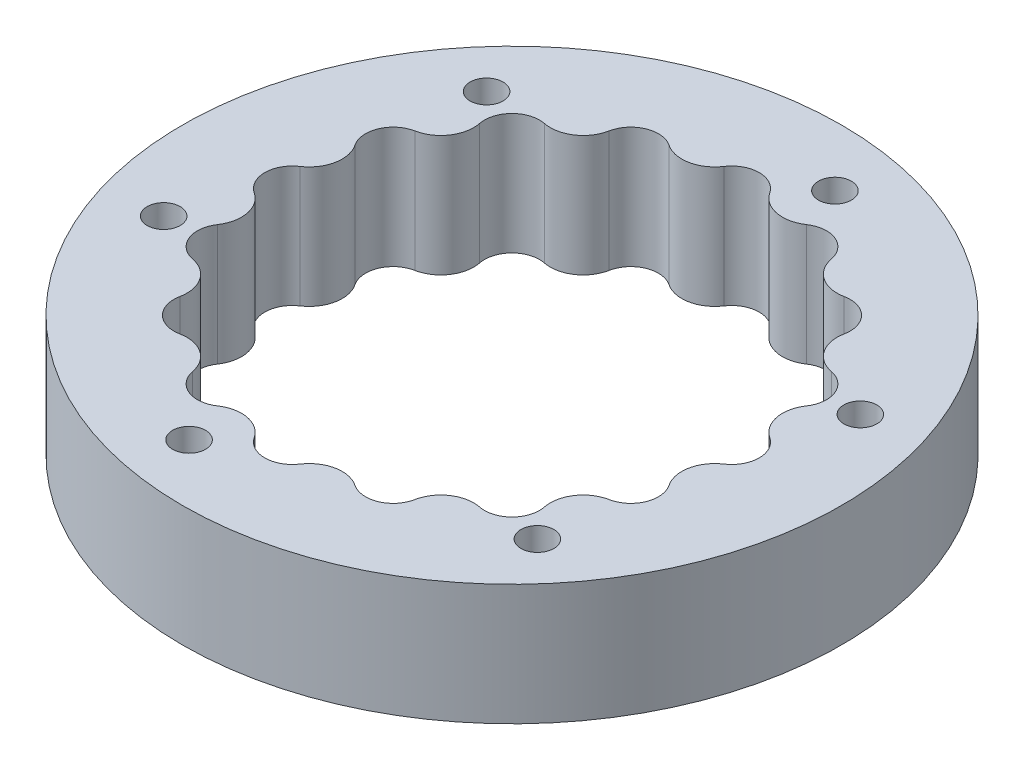
SolidWorks part; units mm, degrees
ref_plane "Front Plane" through (0, 0, 0) normal (0, 0, 1) x (1, 0, 0)
ref_plane "Top Plane" through (0, 0, 0) normal (0, 1, 0) x (1, 0, 0)
ref_plane "Right Plane" through (0, 0, 0) normal (1, 0, 0) x (0, 0, -1)
sketch "Sketch1" plane through (0, 0, 0) normal (0, 1, 0) x (1, 0, 0)
  arc A0 (-31.5919, 24.5347) -> (-34.7568, 19.7981) centre (0, 0) ccw
  arc A1 (4.9902, 39.6875) -> (-4.9902, 39.6875) centre (0, 40) ccw
  arc A2 (19.7981, 34.7568) -> (10.5774, 38.5761) centre (15.3073, 36.9552) ccw
  arc A3 (-31.5919, 24.5347) -> (-34.7568, 19.7981) centre (0, 0) ccw construction
  arc A4 (31.5919, 24.5347) -> (24.5347, 31.5919) centre (28.2843, 28.2843) ccw
  arc A5 (-31.5919, 24.5347) -> (-34.7568, 19.7981) centre (0, 0) ccw construction
  arc A6 (38.5761, 10.5774) -> (34.7568, 19.7981) centre (36.9552, 15.3073) ccw
  arc A7 (-31.5919, 24.5347) -> (-34.7568, 19.7981) centre (0, 0) ccw construction
  arc A8 (39.6875, -4.9902) -> (39.6875, 4.9902) centre (40, 0) ccw
  arc A9 (-31.5919, 24.5347) -> (-34.7568, 19.7981) centre (0, 0) ccw construction
  arc A10 (34.7568, -19.7981) -> (38.5761, -10.5774) centre (36.9552, -15.3073) ccw
  arc A11 (-31.5919, 24.5347) -> (-34.7568, 19.7981) centre (0, 0) ccw construction
  arc A12 (24.5347, -31.5919) -> (31.5919, -24.5347) centre (28.2843, -28.2843) ccw
  arc A13 (-31.5919, 24.5347) -> (-34.7568, 19.7981) centre (0, 0) ccw construction
  arc A14 (10.5774, -38.5761) -> (19.7981, -34.7568) centre (15.3073, -36.9552) ccw
  arc A15 (-31.5919, 24.5347) -> (-34.7568, 19.7981) centre (0, 0) ccw construction
  arc A16 (-4.9902, -39.6875) -> (4.9902, -39.6875) centre (0, -40) ccw
  arc A17 (-31.5919, 24.5347) -> (-34.7568, 19.7981) centre (0, 0) ccw construction
  arc A18 (-19.7981, -34.7568) -> (-10.5774, -38.5761) centre (-15.3073, -36.9552) ccw
  arc A19 (-31.5919, 24.5347) -> (-34.7568, 19.7981) centre (0, 0) ccw construction
  arc A20 (-31.5919, -24.5347) -> (-24.5347, -31.5919) centre (-28.2843, -28.2843) ccw
  arc A21 (-31.5919, 24.5347) -> (-34.7568, 19.7981) centre (0, 0) ccw construction
  arc A22 (-38.5761, -10.5774) -> (-34.7568, -19.7981) centre (-36.9552, -15.3073) ccw
  arc A23 (-31.5919, 24.5347) -> (-34.7568, 19.7981) centre (0, 0) ccw construction
  arc A24 (-39.6875, 4.9902) -> (-39.6875, -4.9902) centre (-40, 0) ccw
  arc A25 (-31.5919, 24.5347) -> (-34.7568, 19.7981) centre (0, 0) ccw construction
  arc A26 (-34.7568, 19.7981) -> (-38.5761, 10.5774) centre (-36.9552, 15.3073) ccw
  arc A27 (-31.5919, 24.5347) -> (-34.7568, 19.7981) centre (0, 0) ccw construction
  arc A28 (-24.5347, 31.5919) -> (-31.5919, 24.5347) centre (-28.2843, 28.2843) ccw
  arc A29 (-31.5919, 24.5347) -> (-34.7568, 19.7981) centre (0, 0) ccw construction
  arc A30 (-10.5774, 38.5761) -> (-19.7981, 34.7568) centre (-15.3073, 36.9552) ccw
  arc A31 (-31.5919, 24.5347) -> (-34.7568, 19.7981) centre (0, 0) ccw construction
  circle A32 centre (0, 0) radius 60
  arc A33 (-19.7981, 34.7568) -> (-24.5347, 31.5919) centre (0, 0) ccw
  arc A34 (-19.7981, 34.7568) -> (-24.5347, 31.5919) centre (0, 0) ccw construction
  arc A35 (-19.7981, 34.7568) -> (-24.5347, 31.5919) centre (0, 0) ccw construction
  arc A36 (-19.7981, 34.7568) -> (-24.5347, 31.5919) centre (0, 0) ccw construction
  arc A37 (-19.7981, 34.7568) -> (-24.5347, 31.5919) centre (0, 0) ccw construction
  arc A38 (-19.7981, 34.7568) -> (-24.5347, 31.5919) centre (0, 0) ccw construction
  arc A39 (-19.7981, 34.7568) -> (-24.5347, 31.5919) centre (0, 0) ccw construction
  arc A40 (-19.7981, 34.7568) -> (-24.5347, 31.5919) centre (0, 0) ccw construction
  arc A41 (-19.7981, 34.7568) -> (-24.5347, 31.5919) centre (0, 0) ccw construction
  arc A42 (-19.7981, 34.7568) -> (-24.5347, 31.5919) centre (0, 0) ccw construction
  arc A43 (-19.7981, 34.7568) -> (-24.5347, 31.5919) centre (0, 0) ccw construction
  arc A44 (-19.7981, 34.7568) -> (-24.5347, 31.5919) centre (0, 0) ccw construction
  arc A45 (-19.7981, 34.7568) -> (-24.5347, 31.5919) centre (0, 0) ccw construction
  arc A46 (-19.7981, 34.7568) -> (-24.5347, 31.5919) centre (0, 0) ccw construction
  arc A47 (-19.7981, 34.7568) -> (-24.5347, 31.5919) centre (0, 0) ccw construction
  arc A48 (-19.7981, 34.7568) -> (-24.5347, 31.5919) centre (0, 0) ccw construction
  arc A49 (-4.9902, 39.6875) -> (-10.5774, 38.5761) centre (0, 0) ccw
  arc A50 (-4.9902, 39.6875) -> (-10.5774, 38.5761) centre (0, 0) ccw construction
  arc A51 (-4.9902, 39.6875) -> (-10.5774, 38.5761) centre (0, 0) ccw construction
  arc A52 (-4.9902, 39.6875) -> (-10.5774, 38.5761) centre (0, 0) ccw construction
  arc A53 (-4.9902, 39.6875) -> (-10.5774, 38.5761) centre (0, 0) ccw construction
  arc A54 (-4.9902, 39.6875) -> (-10.5774, 38.5761) centre (0, 0) ccw construction
  arc A55 (-4.9902, 39.6875) -> (-10.5774, 38.5761) centre (0, 0) ccw construction
  arc A56 (-4.9902, 39.6875) -> (-10.5774, 38.5761) centre (0, 0) ccw construction
  arc A57 (-4.9902, 39.6875) -> (-10.5774, 38.5761) centre (0, 0) ccw construction
  arc A58 (-4.9902, 39.6875) -> (-10.5774, 38.5761) centre (0, 0) ccw construction
  arc A59 (-4.9902, 39.6875) -> (-10.5774, 38.5761) centre (0, 0) ccw construction
  arc A60 (-4.9902, 39.6875) -> (-10.5774, 38.5761) centre (0, 0) ccw construction
  arc A61 (-4.9902, 39.6875) -> (-10.5774, 38.5761) centre (0, 0) ccw construction
  arc A62 (-4.9902, 39.6875) -> (-10.5774, 38.5761) centre (0, 0) ccw construction
  arc A63 (-4.9902, 39.6875) -> (-10.5774, 38.5761) centre (0, 0) ccw construction
  arc A64 (-4.9902, 39.6875) -> (-10.5774, 38.5761) centre (0, 0) ccw construction
  arc A65 (10.5774, 38.5761) -> (4.9902, 39.6875) centre (0, 0) ccw
  arc A66 (10.5774, 38.5761) -> (4.9902, 39.6875) centre (0, 0) ccw construction
  arc A67 (10.5774, 38.5761) -> (4.9902, 39.6875) centre (0, 0) ccw construction
  arc A68 (10.5774, 38.5761) -> (4.9902, 39.6875) centre (0, 0) ccw construction
  arc A69 (10.5774, 38.5761) -> (4.9902, 39.6875) centre (0, 0) ccw construction
  arc A70 (10.5774, 38.5761) -> (4.9902, 39.6875) centre (0, 0) ccw construction
  arc A71 (10.5774, 38.5761) -> (4.9902, 39.6875) centre (0, 0) ccw construction
  arc A72 (10.5774, 38.5761) -> (4.9902, 39.6875) centre (0, 0) ccw construction
  arc A73 (10.5774, 38.5761) -> (4.9902, 39.6875) centre (0, 0) ccw construction
  arc A74 (10.5774, 38.5761) -> (4.9902, 39.6875) centre (0, 0) ccw construction
  arc A75 (10.5774, 38.5761) -> (4.9902, 39.6875) centre (0, 0) ccw construction
  arc A76 (10.5774, 38.5761) -> (4.9902, 39.6875) centre (0, 0) ccw construction
  arc A77 (10.5774, 38.5761) -> (4.9902, 39.6875) centre (0, 0) ccw construction
  arc A78 (10.5774, 38.5761) -> (4.9902, 39.6875) centre (0, 0) ccw construction
  arc A79 (10.5774, 38.5761) -> (4.9902, 39.6875) centre (0, 0) ccw construction
  arc A80 (10.5774, 38.5761) -> (4.9902, 39.6875) centre (0, 0) ccw construction
  arc A81 (24.5347, 31.5919) -> (19.7981, 34.7568) centre (0, 0) ccw
  arc A82 (24.5347, 31.5919) -> (19.7981, 34.7568) centre (0, 0) ccw construction
  arc A83 (24.5347, 31.5919) -> (19.7981, 34.7568) centre (0, 0) ccw construction
  arc A84 (24.5347, 31.5919) -> (19.7981, 34.7568) centre (0, 0) ccw construction
  arc A85 (24.5347, 31.5919) -> (19.7981, 34.7568) centre (0, 0) ccw construction
  arc A86 (24.5347, 31.5919) -> (19.7981, 34.7568) centre (0, 0) ccw construction
  arc A87 (24.5347, 31.5919) -> (19.7981, 34.7568) centre (0, 0) ccw construction
  arc A88 (24.5347, 31.5919) -> (19.7981, 34.7568) centre (0, 0) ccw construction
  arc A89 (24.5347, 31.5919) -> (19.7981, 34.7568) centre (0, 0) ccw construction
  arc A90 (24.5347, 31.5919) -> (19.7981, 34.7568) centre (0, 0) ccw construction
  arc A91 (24.5347, 31.5919) -> (19.7981, 34.7568) centre (0, 0) ccw construction
  arc A92 (24.5347, 31.5919) -> (19.7981, 34.7568) centre (0, 0) ccw construction
  arc A93 (24.5347, 31.5919) -> (19.7981, 34.7568) centre (0, 0) ccw construction
  arc A94 (24.5347, 31.5919) -> (19.7981, 34.7568) centre (0, 0) ccw construction
  arc A95 (24.5347, 31.5919) -> (19.7981, 34.7568) centre (0, 0) ccw construction
  arc A96 (24.5347, 31.5919) -> (19.7981, 34.7568) centre (0, 0) ccw construction
  arc A97 (34.7568, 19.7981) -> (31.5919, 24.5347) centre (0, 0) ccw
  arc A98 (34.7568, 19.7981) -> (31.5919, 24.5347) centre (0, 0) ccw construction
  arc A99 (34.7568, 19.7981) -> (31.5919, 24.5347) centre (0, 0) ccw construction
  arc A100 (34.7568, 19.7981) -> (31.5919, 24.5347) centre (0, 0) ccw construction
  arc A101 (34.7568, 19.7981) -> (31.5919, 24.5347) centre (0, 0) ccw construction
  arc A102 (34.7568, 19.7981) -> (31.5919, 24.5347) centre (0, 0) ccw construction
  arc A103 (34.7568, 19.7981) -> (31.5919, 24.5347) centre (0, 0) ccw construction
  arc A104 (34.7568, 19.7981) -> (31.5919, 24.5347) centre (0, 0) ccw construction
  arc A105 (34.7568, 19.7981) -> (31.5919, 24.5347) centre (0, 0) ccw construction
  arc A106 (34.7568, 19.7981) -> (31.5919, 24.5347) centre (0, 0) ccw construction
  arc A107 (34.7568, 19.7981) -> (31.5919, 24.5347) centre (0, 0) ccw construction
  arc A108 (34.7568, 19.7981) -> (31.5919, 24.5347) centre (0, 0) ccw construction
  arc A109 (34.7568, 19.7981) -> (31.5919, 24.5347) centre (0, 0) ccw construction
  arc A110 (34.7568, 19.7981) -> (31.5919, 24.5347) centre (0, 0) ccw construction
  arc A111 (34.7568, 19.7981) -> (31.5919, 24.5347) centre (0, 0) ccw construction
  arc A112 (34.7568, 19.7981) -> (31.5919, 24.5347) centre (0, 0) ccw construction
  arc A113 (39.6875, 4.9902) -> (38.5761, 10.5774) centre (0, 0) ccw
  arc A114 (39.6875, 4.9902) -> (38.5761, 10.5774) centre (0, 0) ccw construction
  arc A115 (39.6875, 4.9902) -> (38.5761, 10.5774) centre (0, 0) ccw construction
  arc A116 (39.6875, 4.9902) -> (38.5761, 10.5774) centre (0, 0) ccw construction
  arc A117 (39.6875, 4.9902) -> (38.5761, 10.5774) centre (0, 0) ccw construction
  arc A118 (39.6875, 4.9902) -> (38.5761, 10.5774) centre (0, 0) ccw construction
  arc A119 (39.6875, 4.9902) -> (38.5761, 10.5774) centre (0, 0) ccw construction
  arc A120 (39.6875, 4.9902) -> (38.5761, 10.5774) centre (0, 0) ccw construction
  arc A121 (39.6875, 4.9902) -> (38.5761, 10.5774) centre (0, 0) ccw construction
  arc A122 (39.6875, 4.9902) -> (38.5761, 10.5774) centre (0, 0) ccw construction
  arc A123 (39.6875, 4.9902) -> (38.5761, 10.5774) centre (0, 0) ccw construction
  arc A124 (39.6875, 4.9902) -> (38.5761, 10.5774) centre (0, 0) ccw construction
  arc A125 (39.6875, 4.9902) -> (38.5761, 10.5774) centre (0, 0) ccw construction
  arc A126 (39.6875, 4.9902) -> (38.5761, 10.5774) centre (0, 0) ccw construction
  arc A127 (39.6875, 4.9902) -> (38.5761, 10.5774) centre (0, 0) ccw construction
  arc A128 (39.6875, 4.9902) -> (38.5761, 10.5774) centre (0, 0) ccw construction
  arc A129 (38.5761, -10.5774) -> (39.6875, -4.9902) centre (0, 0) ccw
  arc A130 (38.5761, -10.5774) -> (39.6875, -4.9902) centre (0, 0) ccw construction
  arc A131 (38.5761, -10.5774) -> (39.6875, -4.9902) centre (0, 0) ccw construction
  arc A132 (38.5761, -10.5774) -> (39.6875, -4.9902) centre (0, 0) ccw construction
  arc A133 (38.5761, -10.5774) -> (39.6875, -4.9902) centre (0, 0) ccw construction
  arc A134 (38.5761, -10.5774) -> (39.6875, -4.9902) centre (0, 0) ccw construction
  arc A135 (38.5761, -10.5774) -> (39.6875, -4.9902) centre (0, 0) ccw construction
  arc A136 (38.5761, -10.5774) -> (39.6875, -4.9902) centre (0, 0) ccw construction
  arc A137 (38.5761, -10.5774) -> (39.6875, -4.9902) centre (0, 0) ccw construction
  arc A138 (38.5761, -10.5774) -> (39.6875, -4.9902) centre (0, 0) ccw construction
  arc A139 (38.5761, -10.5774) -> (39.6875, -4.9902) centre (0, 0) ccw construction
  arc A140 (38.5761, -10.5774) -> (39.6875, -4.9902) centre (0, 0) ccw construction
  arc A141 (38.5761, -10.5774) -> (39.6875, -4.9902) centre (0, 0) ccw construction
  arc A142 (38.5761, -10.5774) -> (39.6875, -4.9902) centre (0, 0) ccw construction
  arc A143 (38.5761, -10.5774) -> (39.6875, -4.9902) centre (0, 0) ccw construction
  arc A144 (38.5761, -10.5774) -> (39.6875, -4.9902) centre (0, 0) ccw construction
  arc A145 (31.5919, -24.5347) -> (34.7568, -19.7981) centre (0, 0) ccw
  arc A146 (31.5919, -24.5347) -> (34.7568, -19.7981) centre (0, 0) ccw construction
  arc A147 (31.5919, -24.5347) -> (34.7568, -19.7981) centre (0, 0) ccw construction
  arc A148 (31.5919, -24.5347) -> (34.7568, -19.7981) centre (0, 0) ccw construction
  arc A149 (31.5919, -24.5347) -> (34.7568, -19.7981) centre (0, 0) ccw construction
  arc A150 (31.5919, -24.5347) -> (34.7568, -19.7981) centre (0, 0) ccw construction
  arc A151 (31.5919, -24.5347) -> (34.7568, -19.7981) centre (0, 0) ccw construction
  arc A152 (31.5919, -24.5347) -> (34.7568, -19.7981) centre (0, 0) ccw construction
  arc A153 (31.5919, -24.5347) -> (34.7568, -19.7981) centre (0, 0) ccw construction
  arc A154 (31.5919, -24.5347) -> (34.7568, -19.7981) centre (0, 0) ccw construction
  arc A155 (31.5919, -24.5347) -> (34.7568, -19.7981) centre (0, 0) ccw construction
  arc A156 (31.5919, -24.5347) -> (34.7568, -19.7981) centre (0, 0) ccw construction
  arc A157 (31.5919, -24.5347) -> (34.7568, -19.7981) centre (0, 0) ccw construction
  arc A158 (31.5919, -24.5347) -> (34.7568, -19.7981) centre (0, 0) ccw construction
  arc A159 (31.5919, -24.5347) -> (34.7568, -19.7981) centre (0, 0) ccw construction
  arc A160 (31.5919, -24.5347) -> (34.7568, -19.7981) centre (0, 0) ccw construction
  arc A161 (19.7981, -34.7568) -> (24.5347, -31.5919) centre (0, 0) ccw
  arc A162 (19.7981, -34.7568) -> (24.5347, -31.5919) centre (0, 0) ccw construction
  arc A163 (19.7981, -34.7568) -> (24.5347, -31.5919) centre (0, 0) ccw construction
  arc A164 (19.7981, -34.7568) -> (24.5347, -31.5919) centre (0, 0) ccw construction
  arc A165 (19.7981, -34.7568) -> (24.5347, -31.5919) centre (0, 0) ccw construction
  arc A166 (19.7981, -34.7568) -> (24.5347, -31.5919) centre (0, 0) ccw construction
  arc A167 (19.7981, -34.7568) -> (24.5347, -31.5919) centre (0, 0) ccw construction
  arc A168 (19.7981, -34.7568) -> (24.5347, -31.5919) centre (0, 0) ccw construction
  arc A169 (19.7981, -34.7568) -> (24.5347, -31.5919) centre (0, 0) ccw construction
  arc A170 (19.7981, -34.7568) -> (24.5347, -31.5919) centre (0, 0) ccw construction
  arc A171 (19.7981, -34.7568) -> (24.5347, -31.5919) centre (0, 0) ccw construction
  arc A172 (19.7981, -34.7568) -> (24.5347, -31.5919) centre (0, 0) ccw construction
  arc A173 (19.7981, -34.7568) -> (24.5347, -31.5919) centre (0, 0) ccw construction
  arc A174 (19.7981, -34.7568) -> (24.5347, -31.5919) centre (0, 0) ccw construction
  arc A175 (19.7981, -34.7568) -> (24.5347, -31.5919) centre (0, 0) ccw construction
  arc A176 (19.7981, -34.7568) -> (24.5347, -31.5919) centre (0, 0) ccw construction
  arc A177 (4.9902, -39.6875) -> (10.5774, -38.5761) centre (0, 0) ccw
  arc A178 (4.9902, -39.6875) -> (10.5774, -38.5761) centre (0, 0) ccw construction
  arc A179 (4.9902, -39.6875) -> (10.5774, -38.5761) centre (0, 0) ccw construction
  arc A180 (4.9902, -39.6875) -> (10.5774, -38.5761) centre (0, 0) ccw construction
  arc A181 (4.9902, -39.6875) -> (10.5774, -38.5761) centre (0, 0) ccw construction
  arc A182 (4.9902, -39.6875) -> (10.5774, -38.5761) centre (0, 0) ccw construction
  arc A183 (4.9902, -39.6875) -> (10.5774, -38.5761) centre (0, 0) ccw construction
  arc A184 (4.9902, -39.6875) -> (10.5774, -38.5761) centre (0, 0) ccw construction
  arc A185 (4.9902, -39.6875) -> (10.5774, -38.5761) centre (0, 0) ccw construction
  arc A186 (4.9902, -39.6875) -> (10.5774, -38.5761) centre (0, 0) ccw construction
  arc A187 (4.9902, -39.6875) -> (10.5774, -38.5761) centre (0, 0) ccw construction
  arc A188 (4.9902, -39.6875) -> (10.5774, -38.5761) centre (0, 0) ccw construction
  arc A189 (4.9902, -39.6875) -> (10.5774, -38.5761) centre (0, 0) ccw construction
  arc A190 (4.9902, -39.6875) -> (10.5774, -38.5761) centre (0, 0) ccw construction
  arc A191 (4.9902, -39.6875) -> (10.5774, -38.5761) centre (0, 0) ccw construction
  arc A192 (4.9902, -39.6875) -> (10.5774, -38.5761) centre (0, 0) ccw construction
  arc A193 (-10.5774, -38.5761) -> (-4.9902, -39.6875) centre (0, 0) ccw
  arc A194 (-10.5774, -38.5761) -> (-4.9902, -39.6875) centre (0, 0) ccw construction
  arc A195 (-10.5774, -38.5761) -> (-4.9902, -39.6875) centre (0, 0) ccw construction
  arc A196 (-10.5774, -38.5761) -> (-4.9902, -39.6875) centre (0, 0) ccw construction
  arc A197 (-10.5774, -38.5761) -> (-4.9902, -39.6875) centre (0, 0) ccw construction
  arc A198 (-10.5774, -38.5761) -> (-4.9902, -39.6875) centre (0, 0) ccw construction
  arc A199 (-10.5774, -38.5761) -> (-4.9902, -39.6875) centre (0, 0) ccw construction
  arc A200 (-10.5774, -38.5761) -> (-4.9902, -39.6875) centre (0, 0) ccw construction
  arc A201 (-10.5774, -38.5761) -> (-4.9902, -39.6875) centre (0, 0) ccw construction
  arc A202 (-10.5774, -38.5761) -> (-4.9902, -39.6875) centre (0, 0) ccw construction
  arc A203 (-10.5774, -38.5761) -> (-4.9902, -39.6875) centre (0, 0) ccw construction
  arc A204 (-10.5774, -38.5761) -> (-4.9902, -39.6875) centre (0, 0) ccw construction
  arc A205 (-10.5774, -38.5761) -> (-4.9902, -39.6875) centre (0, 0) ccw construction
  arc A206 (-10.5774, -38.5761) -> (-4.9902, -39.6875) centre (0, 0) ccw construction
  arc A207 (-10.5774, -38.5761) -> (-4.9902, -39.6875) centre (0, 0) ccw construction
  arc A208 (-10.5774, -38.5761) -> (-4.9902, -39.6875) centre (0, 0) ccw construction
  arc A209 (-24.5347, -31.5919) -> (-19.7981, -34.7568) centre (0, 0) ccw
  arc A210 (-24.5347, -31.5919) -> (-19.7981, -34.7568) centre (0, 0) ccw construction
  arc A211 (-24.5347, -31.5919) -> (-19.7981, -34.7568) centre (0, 0) ccw construction
  arc A212 (-24.5347, -31.5919) -> (-19.7981, -34.7568) centre (0, 0) ccw construction
  arc A213 (-24.5347, -31.5919) -> (-19.7981, -34.7568) centre (0, 0) ccw construction
  arc A214 (-24.5347, -31.5919) -> (-19.7981, -34.7568) centre (0, 0) ccw construction
  arc A215 (-24.5347, -31.5919) -> (-19.7981, -34.7568) centre (0, 0) ccw construction
  arc A216 (-24.5347, -31.5919) -> (-19.7981, -34.7568) centre (0, 0) ccw construction
  arc A217 (-24.5347, -31.5919) -> (-19.7981, -34.7568) centre (0, 0) ccw construction
  arc A218 (-24.5347, -31.5919) -> (-19.7981, -34.7568) centre (0, 0) ccw construction
  arc A219 (-24.5347, -31.5919) -> (-19.7981, -34.7568) centre (0, 0) ccw construction
  arc A220 (-24.5347, -31.5919) -> (-19.7981, -34.7568) centre (0, 0) ccw construction
  arc A221 (-24.5347, -31.5919) -> (-19.7981, -34.7568) centre (0, 0) ccw construction
  arc A222 (-24.5347, -31.5919) -> (-19.7981, -34.7568) centre (0, 0) ccw construction
  arc A223 (-24.5347, -31.5919) -> (-19.7981, -34.7568) centre (0, 0) ccw construction
  arc A224 (-24.5347, -31.5919) -> (-19.7981, -34.7568) centre (0, 0) ccw construction
  arc A225 (-34.7568, -19.7981) -> (-31.5919, -24.5347) centre (0, 0) ccw
  arc A226 (-34.7568, -19.7981) -> (-31.5919, -24.5347) centre (0, 0) ccw construction
  arc A227 (-34.7568, -19.7981) -> (-31.5919, -24.5347) centre (0, 0) ccw construction
  arc A228 (-34.7568, -19.7981) -> (-31.5919, -24.5347) centre (0, 0) ccw construction
  arc A229 (-34.7568, -19.7981) -> (-31.5919, -24.5347) centre (0, 0) ccw construction
  arc A230 (-34.7568, -19.7981) -> (-31.5919, -24.5347) centre (0, 0) ccw construction
  arc A231 (-34.7568, -19.7981) -> (-31.5919, -24.5347) centre (0, 0) ccw construction
  arc A232 (-34.7568, -19.7981) -> (-31.5919, -24.5347) centre (0, 0) ccw construction
  arc A233 (-34.7568, -19.7981) -> (-31.5919, -24.5347) centre (0, 0) ccw construction
  arc A234 (-34.7568, -19.7981) -> (-31.5919, -24.5347) centre (0, 0) ccw construction
  arc A235 (-34.7568, -19.7981) -> (-31.5919, -24.5347) centre (0, 0) ccw construction
  arc A236 (-34.7568, -19.7981) -> (-31.5919, -24.5347) centre (0, 0) ccw construction
  arc A237 (-34.7568, -19.7981) -> (-31.5919, -24.5347) centre (0, 0) ccw construction
  arc A238 (-34.7568, -19.7981) -> (-31.5919, -24.5347) centre (0, 0) ccw construction
  arc A239 (-34.7568, -19.7981) -> (-31.5919, -24.5347) centre (0, 0) ccw construction
  arc A240 (-34.7568, -19.7981) -> (-31.5919, -24.5347) centre (0, 0) ccw construction
  arc A241 (-39.6875, -4.9902) -> (-38.5761, -10.5774) centre (0, 0) ccw
  arc A242 (-39.6875, -4.9902) -> (-38.5761, -10.5774) centre (0, 0) ccw construction
  arc A243 (-39.6875, -4.9902) -> (-38.5761, -10.5774) centre (0, 0) ccw construction
  arc A244 (-39.6875, -4.9902) -> (-38.5761, -10.5774) centre (0, 0) ccw construction
  arc A245 (-39.6875, -4.9902) -> (-38.5761, -10.5774) centre (0, 0) ccw construction
  arc A246 (-39.6875, -4.9902) -> (-38.5761, -10.5774) centre (0, 0) ccw construction
  arc A247 (-39.6875, -4.9902) -> (-38.5761, -10.5774) centre (0, 0) ccw construction
  arc A248 (-39.6875, -4.9902) -> (-38.5761, -10.5774) centre (0, 0) ccw construction
  arc A249 (-39.6875, -4.9902) -> (-38.5761, -10.5774) centre (0, 0) ccw construction
  arc A250 (-39.6875, -4.9902) -> (-38.5761, -10.5774) centre (0, 0) ccw construction
  arc A251 (-39.6875, -4.9902) -> (-38.5761, -10.5774) centre (0, 0) ccw construction
  arc A252 (-39.6875, -4.9902) -> (-38.5761, -10.5774) centre (0, 0) ccw construction
  arc A253 (-39.6875, -4.9902) -> (-38.5761, -10.5774) centre (0, 0) ccw construction
  arc A254 (-39.6875, -4.9902) -> (-38.5761, -10.5774) centre (0, 0) ccw construction
  arc A255 (-39.6875, -4.9902) -> (-38.5761, -10.5774) centre (0, 0) ccw construction
  arc A256 (-39.6875, -4.9902) -> (-38.5761, -10.5774) centre (0, 0) ccw construction
  arc A257 (-38.5761, 10.5774) -> (-39.6875, 4.9902) centre (0, 0) ccw
  arc A258 (-38.5761, 10.5774) -> (-39.6875, 4.9902) centre (0, 0) ccw construction
  arc A259 (-38.5761, 10.5774) -> (-39.6875, 4.9902) centre (0, 0) ccw construction
  arc A260 (-38.5761, 10.5774) -> (-39.6875, 4.9902) centre (0, 0) ccw construction
  arc A261 (-38.5761, 10.5774) -> (-39.6875, 4.9902) centre (0, 0) ccw construction
  arc A262 (-38.5761, 10.5774) -> (-39.6875, 4.9902) centre (0, 0) ccw construction
  arc A263 (-38.5761, 10.5774) -> (-39.6875, 4.9902) centre (0, 0) ccw construction
  arc A264 (-38.5761, 10.5774) -> (-39.6875, 4.9902) centre (0, 0) ccw construction
  arc A265 (-38.5761, 10.5774) -> (-39.6875, 4.9902) centre (0, 0) ccw construction
  arc A266 (-38.5761, 10.5774) -> (-39.6875, 4.9902) centre (0, 0) ccw construction
  arc A267 (-38.5761, 10.5774) -> (-39.6875, 4.9902) centre (0, 0) ccw construction
  arc A268 (-38.5761, 10.5774) -> (-39.6875, 4.9902) centre (0, 0) ccw construction
  arc A269 (-38.5761, 10.5774) -> (-39.6875, 4.9902) centre (0, 0) ccw construction
  arc A270 (-38.5761, 10.5774) -> (-39.6875, 4.9902) centre (0, 0) ccw construction
  arc A271 (-38.5761, 10.5774) -> (-39.6875, 4.9902) centre (0, 0) ccw construction
  arc A272 (-38.5761, 10.5774) -> (-39.6875, 4.9902) centre (0, 0) ccw construction
  point P52 (0, 0)
  dimension "D1" = 80
  dimension "D2" = 10
  dimension "D4" = 120
  dimension "D3" = 16
extrude "Boss-Extrude1" add sketch "Sketch1" along normal blind 22
fillet "Fillet1" radius 5 32 edges at (-31.5919, 11, -24.5347) (-34.7568, 11, -19.7981) (10.5774, 11, 38.5761) (4.9902, 11, 39.6875) (-4.9902, 11, 39.6875) (-10.5774, 11, 38.5761) (-19.7981, 11, 34.7568) (-24.5347, 11, 31.5919) (-31.5919, 11, 24.5347) (-34.7568, 11, 19.7981) (-38.5761, 11, 10.5774) (-39.6875, 11, 4.9902) (-39.6875, 11, -4.9902) (-38.5761, 11, -10.5774) (19.7981, 11, 34.7568) (24.5347, 11, 31.5919) (31.5919, 11, 24.5347) (34.7568, 11, 19.7981) (38.5761, 11, 10.5774) (39.6875, 11, 4.9902) (39.6875, 11, -4.9902) (38.5761, 11, -10.5774) (34.7568, 11, -19.7981) (31.5919, 11, -24.5347) (24.5347, 11, -31.5919) (19.7981, 11, -34.7568) (10.5774, 11, -38.5761) (4.9902, 11, -39.6875) (-4.9902, 11, -39.6875) (-10.5774, 11, -38.5761) (-19.7981, 11, -34.7568) (-24.5347, 11, -31.5919)
fillet "Fillet2" radius 6 16 edges at (-7.8059, 11, 39.2431) (7.8059, 11, 39.2431) (22.2294, 11, 33.2687) (33.2687, 11, 22.2294) (-22.2294, 11, 33.2687) (-33.2687, 11, 22.2294) (-39.2431, 11, 7.8059) (-39.2431, 11, -7.8059) (39.2431, 11, 7.8059) (39.2431, 11, -7.8059) (33.2687, 11, -22.2294) (22.2294, 11, -33.2687) (7.8059, 11, -39.2431) (-7.8059, 11, -39.2431) (-22.2294, 11, -33.2687) (-33.2687, 11, -22.2294)
sketch "Sketch3" plane through (0, 22, 0) normal (0, 1, 0) x (1, 0, 0)
  line L0 (7.9956, 40.1966) -> (11.7054, 58.8471) construction
  circle A0 centre (0, 0) radius 50 construction
  circle A4 centre (9.7545, 49.0393) radius 3
  arc A5 (4.1664, 42.7642) -> (12.5159, 41.1034) centre (9.1661, 46.0813) ccw construction
  circle A6 centre (0, 0) radius 60 construction
  circle A7 centre (47.3465, 16.072) radius 3
  circle A8 centre (37.592, -32.9673) radius 3
  circle A9 centre (-9.7545, -49.0393) radius 3
  circle A10 centre (-47.3465, -16.072) radius 3
  circle A11 centre (-37.592, 32.9673) radius 3
  point P13 (9.1661, 46.0813)
  point P31 (0, 0)
  dimension "D1" = 100
  dimension "D2" = 6
  dimension "D3" = 6
extrude "Cut-Extrude1" cut sketch "Sketch3" against normal through all
equation "\"R_ROLL\"= 5mm"
equation "\"D_SUN\"= 80mm"
equation "\"NUM_ROLL\"= 16"
equation "\"RHO\"= 1mm"
equation "\"D_SHAFT\"= 15mm"
equation "\"D_OUTPUT\"= 40mm"
equation "\"NUM_OUT\"= 6"
equation "\"R_OUT_ROLL\"= 5mm"
equation "\"D1@Sketch1\"=\"D_SUN\""
equation "\"D2@Sketch1\"=\"R_ROLL\"*2"
equation "\"D3@Sketch1\"=\"NUM_ROLL\""
equation "\"D4@Sketch1\"=\"D_SUN\"+40"
